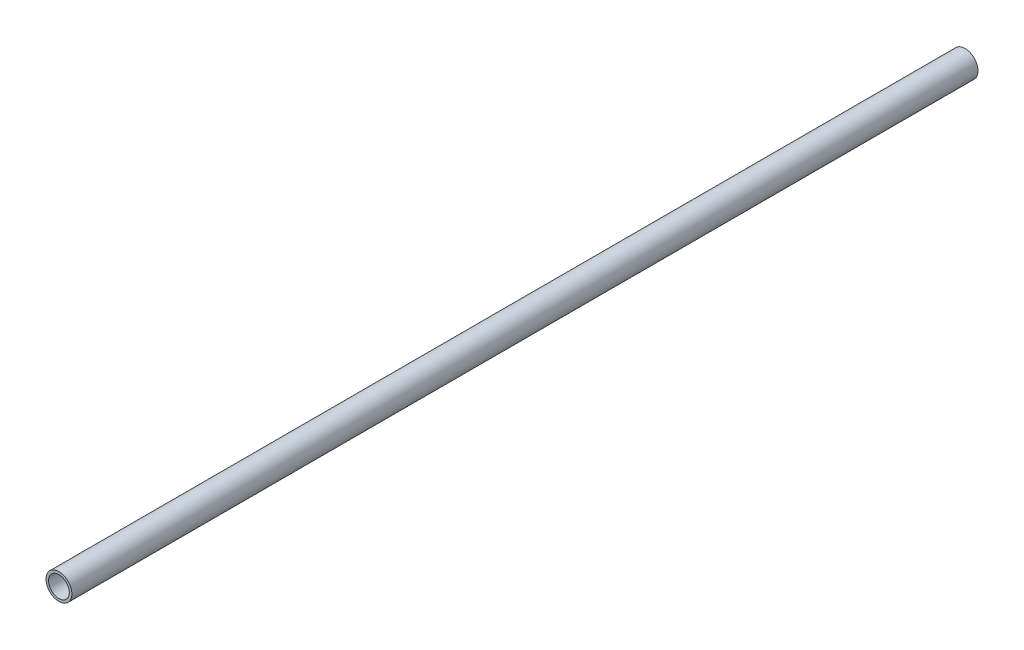
SolidWorks part; units mm, degrees
material "无缝钢管 45"
ref_plane "前视基准面" through (0, 0, 0) normal (0, 0, 1) x (1, 0, 0)
ref_plane "上视基准面" through (0, 0, 0) normal (0, 1, 0) x (1, 0, 0)
ref_plane "右视基准面" through (0, 0, 0) normal (1, 0, 0) x (0, 0, -1)
sketch "草图1" plane through (0, 0, 0) normal (0, 0, 1) x (1, 0, 0)
  circle A0 centre (0, 0) radius 5
  dimension "D1" = 10
extrude "凸台-拉伸1" add sketch "草图1" along normal blind 350
sketch "草图2" plane through (0, 0, 0) normal (0, 0, -1) x (-1, 0, 0)
  circle A1 centre (0, 0) radius 4
  dimension "D1" = 8
extrude "切除-拉伸1" cut sketch "草图2" against normal through all
ref_axis "基准轴1" through (0, 0, 57.5622) along (0, 0, 1)
